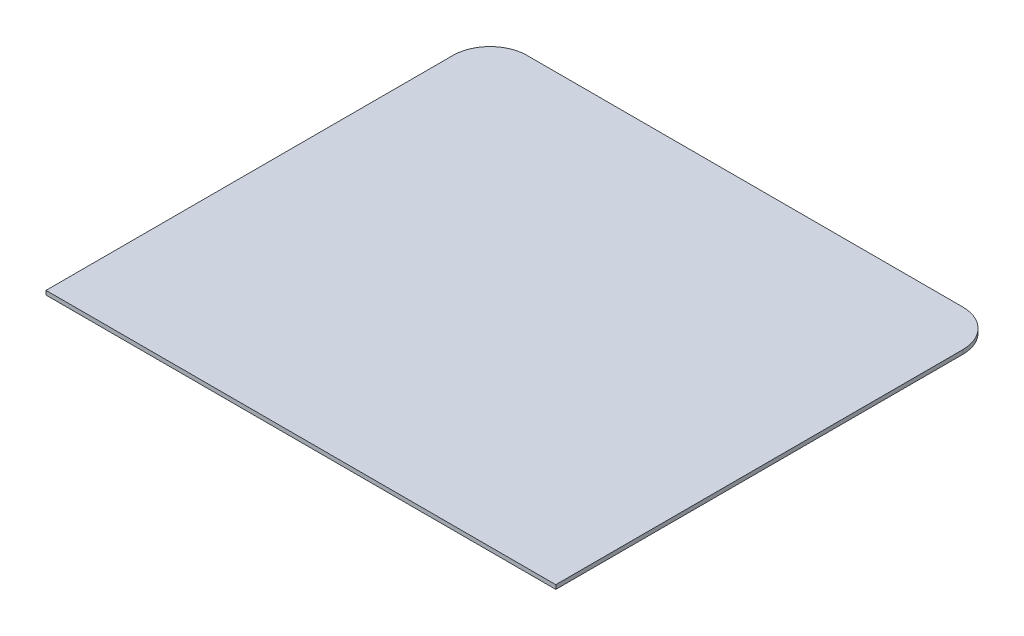
SolidWorks part; units mm, degrees
material "6061-T6 (SS)"
ref_plane "Front" through (0, 0, 0) normal (0, 0, 1) x (1, 0, 0)
ref_plane "Top" through (0, 0, 0) normal (0, 1, 0) x (1, 0, 0)
ref_plane "Right" through (0, 0, 0) normal (1, 0, 0) x (0, 0, -1)
sketch "Sketch1" plane through (0, 0, 0) normal (0, 1, 0) x (1, 0, 0)
  line L1 (196.85, -171.45) -> (-196.85, -171.45)
  line L2 (196.85, -171.45) -> (196.85, 171.45)
  line L3 (196.85, 171.45) -> (-196.85, 171.45)
  line L4 (-196.85, -171.45) -> (-196.85, 171.45)
  line L5 (196.85, -171.45) -> (-196.85, 171.45) construction
  line L6 (196.85, 171.45) -> (-196.85, -171.45) construction
  point P0 (0, 0)
  dimension "D1" = 393.7
  dimension "D2" = 342.9
extrude "Boss-Extrude1" add sketch "Sketch1" along normal blind 3.175
fillet "Fillet1" radius 28.575 2 edges at (-196.85, 1.5875, -171.45) (196.85, 1.5875, -171.45)
